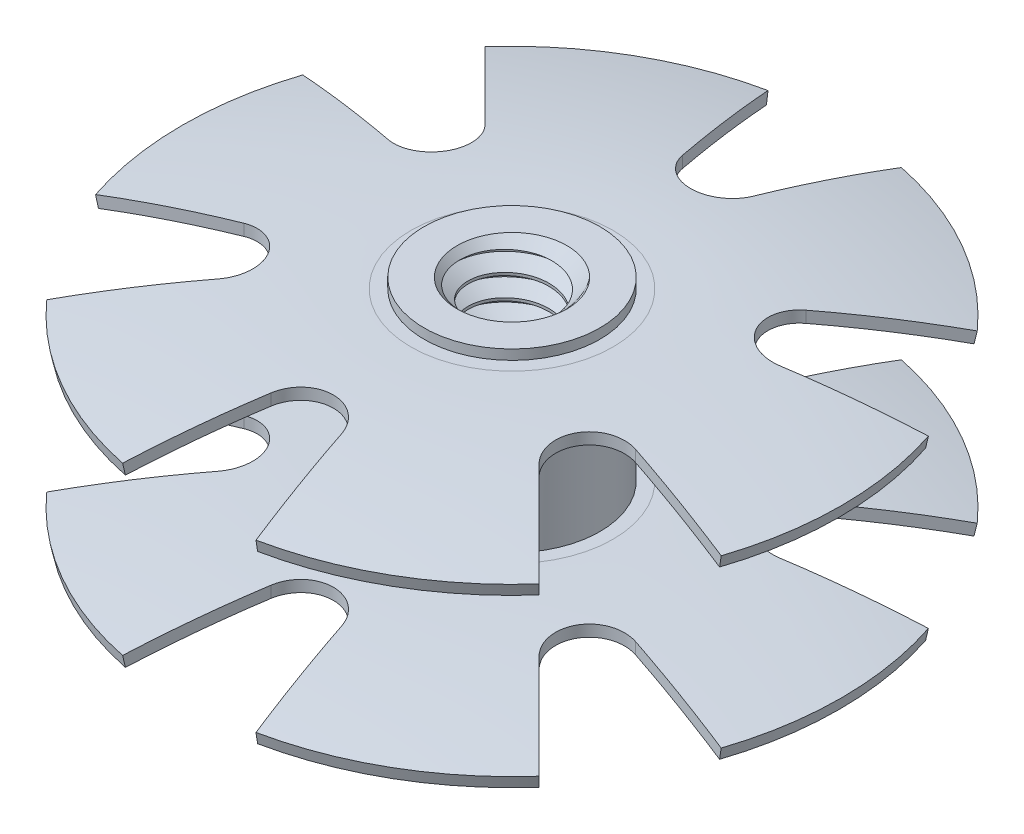
SolidWorks part; units mm, degrees
note: '?' marks a value the reader was unsure of.
ref_plane "Front Plane" through (0, 0, 0) normal (0, 0, 1) x (1, 0, 0)
ref_plane "Top Plane" through (0, 0, 0) normal (0, 1, 0) x (1, 0, 0)
ref_plane "Right Plane" through (0, 0, 0) normal (1, 0, 0) x (0, 0, -1)
sketch "Sketch1" plane through (0, 0, 0) normal (0, 0, 1) x (1, 0, 0)
  line L0 (0, 0) -> (0, 5.715) construction
  line L1 (-5.08, 5.715) -> (-3.175, 5.715)
  line L2 (-5.08, 5.715) -> (-5.08, 5.1435)
  line L3 (-5.08, -5.715) -> (-3.175, -5.715)
  line L4 (-3.175, 5.715) -> (-3.175, -5.715)
  line L5 (0, 0) -> (-3.175, 0) construction
  line L6 (-5.08, -5.1435) -> (-5.08, -5.715)
  line L7 (-5.08, 5.1435) -> (-4.572, 5.1435)
  line L9 (-5.08, 4.4831) -> (-4.572, 4.4831)
  line L10 (-4.572, 5.1435) -> (-4.572, 4.4831)
  line L11 (-5.08, -4.4831) -> (-4.572, -4.4831)
  line L12 (-5.08, 4.4831) -> (-5.08, -4.4831)
  line L13 (-5.08, -5.1435) -> (-4.572, -5.1435)
  line L14 (-4.572, -4.4831) -> (-4.572, -5.1435)
  dimension "ID" = 6.35
  dimension "D1" = 10.16
  dimension "D2" = 11.43
  dimension "D3" = 0.6604
  dimension "D4" = 10.287
  dimension "D5" = 9.144
revolve "Revolve1" add sketch "Sketch1" angle 360 about L0
sketch "Sketch2" plane through (0, 5.715, 0) normal (0, 1, 0) x (1, 0, 0)
  circle A0 centre (0, 0) radius 3.175 construction
  circle A1 centre (0, 0) radius 3.175
sketch "Sketch6" plane through (0, -5.715, 0) normal (0, -1, 0) x (1, 0, 0)
  circle A1 centre (0, 0) radius 3.175
  circle A2 centre (0, 0) radius 3.175
  dimension "D1" = 0
sketch "Sketch8" plane through (0, 0, 0) normal (0, 0, 1) x (1, 0, 0)
  line L0 (-5.08, 4.4831) -> (-4.572, 4.4831) construction
  line L1 (-5.842, 5.1435) -> (-4.572, 5.1435)
  line L2 (-18.9179, 3.1623) -> (-19.05, 3.8094)
  line L3 (-5.842, 4.4831) -> (-4.572, 4.4831)
  line L4 (-4.572, 5.1435) -> (-4.572, 4.4831)
  line L5 (0, 0) -> (0, 5.715) construction
  line L6 (-5.842, -4.4831) -> (-4.572, -4.4831)
  line L7 (-18.9179, -6.4643) -> (-19.05, -5.8172)
  line L8 (-5.842, -5.1435) -> (-4.572, -5.1435)
  line L9 (-4.572, -4.4831) -> (-4.572, -5.1435)
  arc A0 (-5.842, 4.4831) -> (-18.9179, 3.1623) centre (-5.842, -60.9032) ccw
  arc A1 (-5.842, 5.1435) -> (-19.05, 3.8094) centre (-5.842, -60.9032) ccw
  arc A2 (-5.842, -5.1435) -> (-18.9179, -6.4643) centre (-5.842, -70.5298) ccw
  arc A3 (-5.842, -4.4831) -> (-19.05, -5.8172) centre (-5.842, -70.5298) ccw
  dimension "D1" = 11.684
  dimension "D2" = 1.9812
revolve "Revolve2" add sketch "Sketch8" angle 360 about L5
sketch "Sketch9" plane through (0, 5.715, 0) normal (0, 1, 0) x (1, 0, 0)
  line L0 (0, 5.842) -> (0, 19.05) construction
  line L1 (-2.0445, 11.8982) -> (-3.8553, 18.6558)
  line L2 (2.0445, 11.8982) -> (3.8553, 18.6558)
  circle A0 centre (0, 0) radius 5.842 construction
  circle A1 centre (0, 0) radius 19.05 construction
  arc A2 (-2.0445, 11.8982) -> (2.0445, 11.8982) centre (0, 12.446) ccw
  arc A3 (3.8553, 18.6558) -> (-3.8553, 18.6558) centre (0, 0) ccw
  dimension "D1" = 2.1167
  dimension "D2" = 15
extrude "Cut-Extrude5" cut sketch "Sketch9" against normal through all
pattern_circular "CirPattern1" count 6 over 360 about axis through (0, 0, 0) along (0, 1, 0) of "Cut-Extrude5"
sketch "Sketch10" plane through (0, 5.715, 0) normal (0, 1, 0) x (1, 0, 0)
  line L0 (0, 0) -> (2.2451, 2.2451) construction
  line L2 (0, -6.9606) -> (0, 6.9606) construction
  circle A0 centre (0, 0) radius 19.05
  circle A1 centre (0, 0) radius 3.175 construction
  dimension "D1" = 45
curve "Helix/Spiral1" pitch 1.27 height 14.605 turns 11.5 parameters "pitch"=1.27
sketch "Sketch3" plane through (0, 0, 0) normal (0, 0, 1) x (1, 0, 0)
  line L0 (2.3501, 6.35) -> (2.3501, 6.1913)
  line L1 (2.3501, 6.1913) -> (3.175, 5.715)
  line L2 (3.175, 5.715) -> (3.175, 6.8263)
  line L3 (2.3501, 6.35) -> (3.175, 6.8263)
  line L4 (2.3501, 6.2706) -> (3.175, 6.2706) construction
  line L5 (2.7626, 6.5881) -> (2.7626, 5.9531) construction
  dimension "D1" = 0.1588
  dimension "D2" = 0.635
  dimension "D3" = 60
sweep "Sweep1" add profiles "Sketch3" path "Helix/Spiral1"
sketch "Sketch4" plane through (0, 5.715, 0) normal (0, 1, 0) x (1, 0, 0)
  circle A1 centre (0, 0) radius 5.08
  circle A2 centre (0, 0) radius 5.08
  dimension "D1" = 0
extrude "Cut-Extrude1" cut sketch "Sketch4" along normal through all
sketch "Sketch5" plane through (0, -5.715, 0) normal (0, -1, 0) x (1, 0, 0)
  circle A1 centre (0, 0) radius 5.08
  circle A2 centre (0, 0) radius 5.08
  dimension "D1" = 0
extrude "Cut-Extrude2" cut sketch "Sketch5" along normal through all
extrude "Cut-Extrude3" cut sketch "Sketch6" against normal through all draft 45
sketch "Sketch7" plane through (0, 5.715, 0) normal (0, 1, 0) x (1, 0, 0)
  circle A1 centre (0, 0) radius 3.175
  circle A2 centre (0, 0) radius 3.175
  dimension "D1" = 0
extrude "Cut-Extrude4" cut sketch "Sketch7" against normal through all draft 45
ref_plane "Contact Plane 1" through (0, 5.715, 0) normal (0, 1, 0) x (1, 0, 0)
ref_plane "Contact Plane 2" through (0, -5.715, 0) normal (0, -1, 0) x (-1, 0, 0)
ref_axis "Center Axis 1" through (0, 4.4831, 0) along (0, -1, 0)?
equation "\"D1@Sketch1\" = \"ID@Sketch1\"*1.6"
equation "\"D2@Sketch1\" = \"ID@Sketch1\"*1.8"
equation "\"D4@Sketch1\" = \"D2@Sketch1\"*.9"
equation "\"D5@Sketch1\" = \"D1@Sketch1\"*.9"
equation "\"D3@Helix/Spiral1\" = \"D2@Sketch1\"+.125"
equation "\"D1@Sketch3\" = \"pitch@Helix/Spiral1\"*.125"
equation "\"D2@Sketch3\" = \"pitch@Helix/Spiral1\"*.5"
equation "\"D1@Sketch8\" = \"D1@Sketch1\"*1.15"
equation "\"D1@Sketch9\" = \"OD@Sketch8\"/18"
